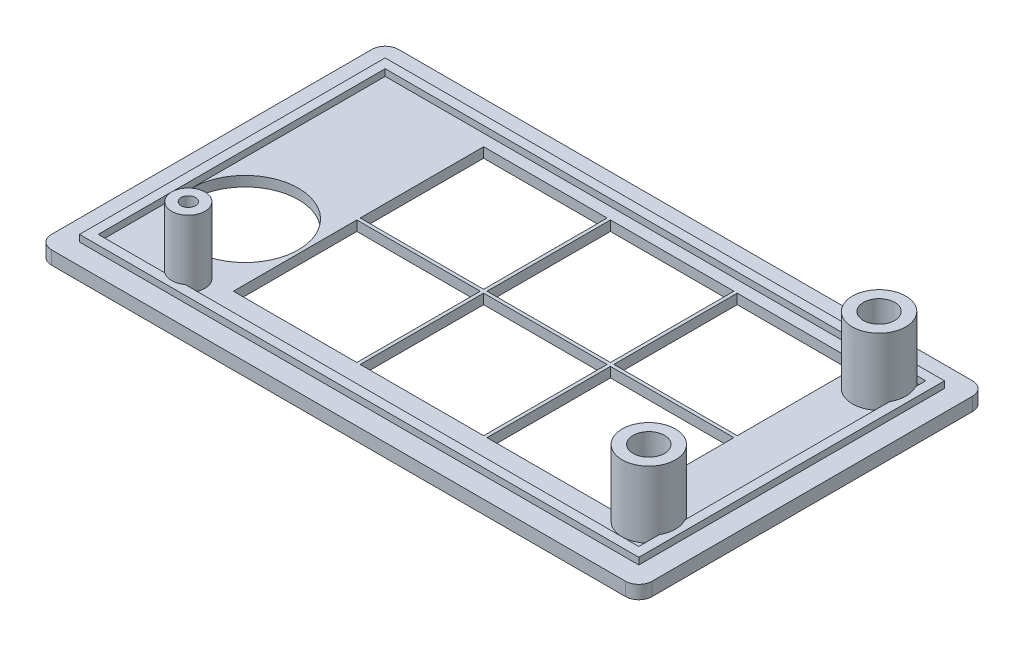
SolidWorks part; units mm, degrees
ref_plane "Front Plane" through (0, 0, 0) normal (0, 0, 1) x (1, 0, 0)
ref_plane "Top Plane" through (0, 0, 0) normal (0, 1, 0) x (1, 0, 0)
ref_plane "Right Plane" through (0, 0, 0) normal (1, 0, 0) x (0, 0, -1)
sketch "Sketch3" plane through (0, 0, 0) normal (0, 1, 0) x (1, 0, 0)
  line L0 (-45, 26) -> (45, 26)
  line L1 (-45, 26) -> (-45, -26)
  line L2 (-45, -26) -> (45, -26)
  line L3 (45, 26) -> (45, -26)
  dimension "D1" = 90
  dimension "D2" = 52
  dimension "D3" = 45
  dimension "D4" = 26
extrude "Boss-Extrude2" add sketch "Sketch3" along normal blind 2
fillet "Fillet2" radius 2 4 edges at (-45, 1, 26) (45, 1, 26) (45, 1, -26) (-45, 1, -26)
sketch "Sketch4" plane through (0, 0, 0) normal (0, 1, 0) x (1, 0, 0)
  line L1 (-41.5, 22.5) -> (41.5, 22.5)
  line L2 (-41.5, 22.5) -> (-41.5, -22.5)
  line L3 (-41.5, -22.5) -> (41.5, -22.5)
  line L4 (41.5, 22.5) -> (41.5, -22.5)
  dimension "D1" = 83
  dimension "D2" = 45
  dimension "D3" = 41.5
  dimension "D4" = 22.5
sketch "Sketch5" plane through (0, 0, 0) normal (0, 1, 0) x (1, 0, 0)
  line L46 (-41.5, 22.5) -> (-41.5, -22.5) construction
  line L47 (-41.5, -22.5) -> (41.5, -22.5) construction
  line L102 (-24, 19.75) -> (-5.5, 19.75)
  line L103 (32.5, 19.75) -> (32.5, 1.25)
  line L104 (-24, -17.75) -> (-5.5, -17.75)
  line L105 (-24, 19.75) -> (-24, 1.25)
  line L106 (-24, 0.75) -> (-24, -17.75)
  line L107 (-24, 1.25) -> (-5.5, 1.25)
  line L109 (-24, 0.75) -> (-5.5, 0.75)
  line L111 (32.5, 0.75) -> (32.5, -17.75)
  line L112 (-5, 19.75) -> (13.5, 19.75)
  line L114 (-5.5, 19.75) -> (-5.5, 1.25)
  line L116 (-5, 19.75) -> (-5, 1.25)
  line L118 (13.5, 19.75) -> (13.5, 1.25)
  line L120 (14, 19.75) -> (14, 1.25)
  line L121 (14, 19.75) -> (32.5, 19.75)
  line L122 (14, 1.25) -> (32.5, 1.25)
  line L123 (14, 0.75) -> (32.5, 0.75)
  line L124 (-5, 1.25) -> (13.5, 1.25)
  line L125 (-5, 0.75) -> (13.5, 0.75)
  line L126 (-5, 0.75) -> (-5, -17.75)
  line L127 (-5.5, 0.75) -> (-5.5, -17.75)
  line L128 (13.5, 0.75) -> (13.5, -17.75)
  line L129 (14, 0.75) -> (14, -17.75)
  line L130 (-5, -17.75) -> (13.5, -17.75)
  line L131 (14, -17.75) -> (32.5, -17.75)
  circle A32 centre (-32.5, -7.5) radius 8
  dimension "D3" = 56.5
  dimension "D11" = 0.5
  dimension "D16" = 9
  dimension "D14" = 16
  dimension "D2" = 24
  dimension "D4" = 37.5
  dimension "D5" = 19.75
  dimension "D6" = 0.5
  dimension "D7" = 18.5
  dimension "D8" = 18.5
  dimension "D9" = 18.5
  dimension "D10" = 18.5
  dimension "D15" = 15
sketch "Sketch7" plane through (0, 0, 0) normal (0, 1, 0) x (1, 0, 0)
  line L2 (41.5, 22.5) -> (41.5, -22.5) construction
  line L3 (-41.5, -22.5) -> (41.5, -22.5) construction
  circle A0 centre (37, 18) radius 4
  circle A3 centre (37, -16.5) radius 4
  dimension "D4" = 4.5
  dimension "D5" = 6
extrude "Boss-Extrude3" add sketch "Sketch7" along normal blind 10 from surface starting at face at (0, 2, 0)
sketch "Sketch8" plane through (0, 0, 0) normal (0, 1, 0) x (1, 0, 0)
  circle A1 centre (37, 18) radius 2.35
  circle A2 centre (37, -16.5) radius 2.35
  dimension "D1" = 4.7
extrude "Cut-Extrude2" cut sketch "Sketch8" against normal blind 5 and the other way through all from surface starting at face at (37, 12, -14)
sketch "Sketch10" plane through (0, 0, 0) normal (0, 1, 0) x (1, 0, 0)
  line L4 (40.5, 21.5) -> (-40.5, 21.5)
  line L5 (-40.5, 21.5) -> (-40.5, -21.5)
  line L6 (-40.5, -21.5) -> (40.5, -21.5)
  line L7 (40.5, -21.5) -> (40.5, 21.5)
  line L8 (41.9, 22.9) -> (-41.9, 22.9)
  line L9 (41.9, -22.9) -> (41.9, 22.9)
  line L10 (-41.9, -22.9) -> (41.9, -22.9)
  line L11 (-41.9, 22.9) -> (-41.9, -22.9)
  line L12 (41.9, 22.9) -> (-41.9, 22.9)
  line L13 (41.9, -22.9) -> (41.9, 22.9)
  line L14 (-41.9, -22.9) -> (41.9, -22.9)
  line L15 (-41.9, 22.9) -> (-41.9, -22.9)
  dimension "D1" = 0.4
  dimension "D2" = 1.4
extrude "Boss-Extrude4" add sketch "Sketch10" along normal blind 1 from surface starting at face at (37, 2, -14)
sketch "Sketch11" plane through (0, 0, 0) normal (0, 1, 0) x (1, 0, 0)
  line L0 (-41.5, -22.5) -> (41.5, -22.5) construction
  circle A0 centre (-29, -19.5) radius 2.5
  dimension "D2" = 5
  dimension "D1" = 3
  dimension "D3" = 11.5
extrude "Boss-Extrude5" add sketch "Sketch11" along normal blind 10 from surface starting at face at (14.9933, 2, 2.9352)
sketch "Sketch12" plane through (0, 0, 0) normal (0, 1, 0) x (1, 0, 0)
  circle A0 centre (-29, -19.5) radius 1.075
  dimension "D1" = 2.15
extrude "Cut-Extrude3" cut sketch "Sketch12" against normal blind 10 from surface starting at face at (-29, 12, 22)
extrude "Cut-Extrude4" cut sketch "Sketch4" along normal blind 0.5
extrude "Cut-Extrude5" cut sketch "Sketch5" along normal through all both and the other way through all
